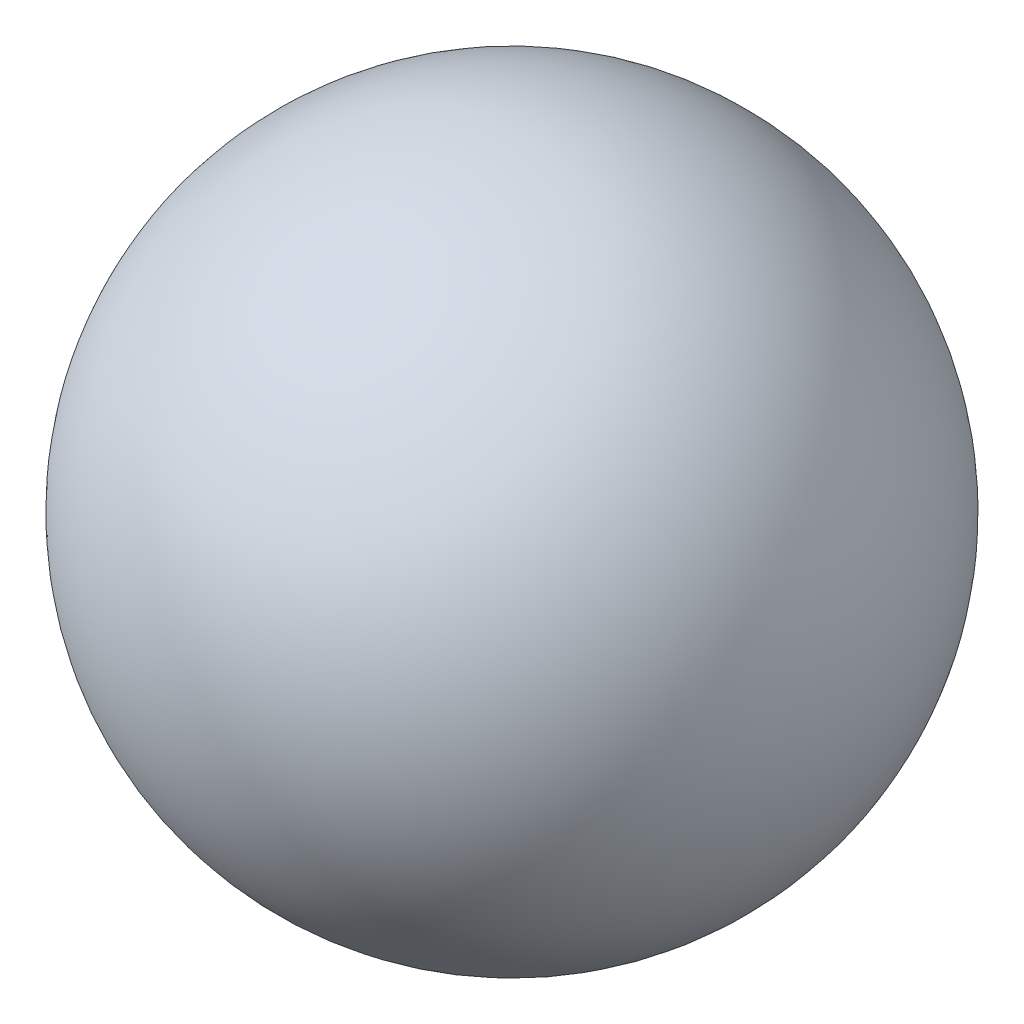
SolidWorks part; units mm, degrees
note: '?' marks a value the reader was unsure of.
ref_plane "Front Plane" through (0, 0, 0) normal (0, 0, 1) x (1, 0, 0)
ref_plane "Top Plane" through (0, 0, 0) normal (0, 1, 0) x (1, 0, 0)
ref_plane "Right Plane" through (0, 0, 0) normal (1, 0, 0) x (0, 0, -1)
sketch "Sketch1" plane through (0, 0, 0) normal (0, 0, 1) x (1, 0, 0)
  line L0 (-7.95, 0) -> (7.95, 0)
  circle A0 centre (0, 0) radius 7.95
  dimension "D1" = 15.9
revolve "Revolve1" add sketch "Sketch1" angle 360 about L0
ref_axis "Axis1" through (-7.645, 0, 0) along (1, 0, 0)?
